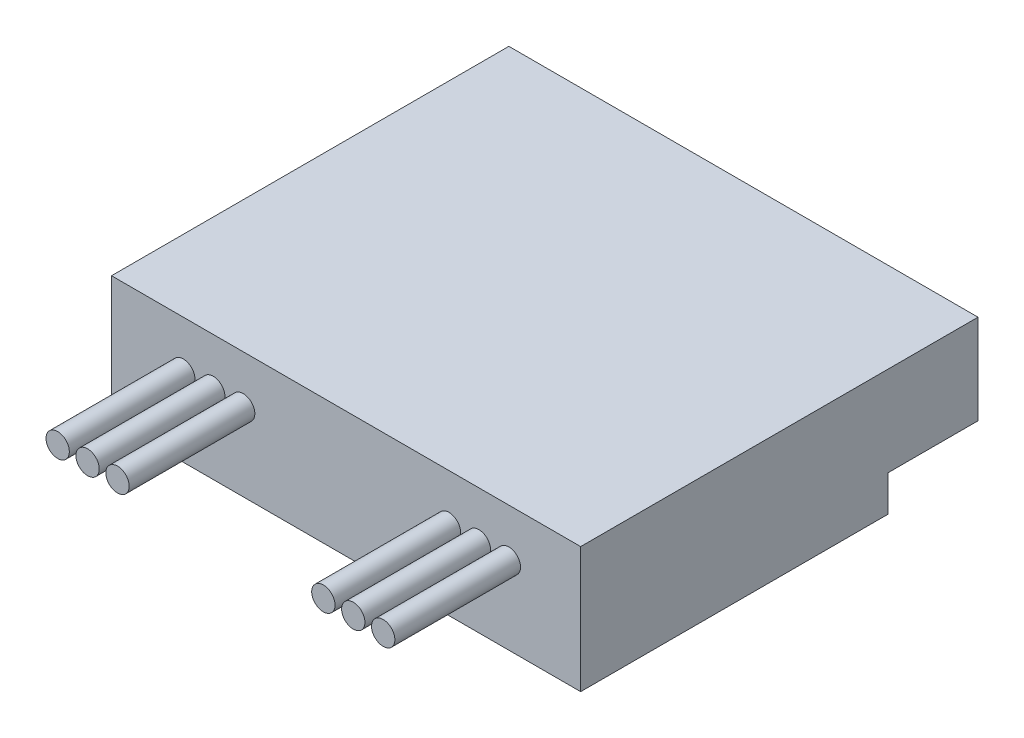
SolidWorks part; units mm, degrees
ref_plane "Front Plane" through (0, 0, 0) normal (0, 0, 1) x (1, 0, 0)
ref_plane "Top Plane" through (0, 0, 0) normal (0, 1, 0) x (1, 0, 0)
ref_plane "Right Plane" through (0, 0, 0) normal (1, 0, 0) x (0, 0, -1)
sketch "Sketch1" plane through (0, 0, 0) normal (0, 1, 0) x (1, 0, 0)
  line L1 (0, 0) -> (78.4, 0)
  line L2 (0, 0) -> (0, 66.4)
  line L3 (0, 66.4) -> (78.4, 66.4)
  line L4 (78.4, 0) -> (78.4, 66.4)
  dimension "D1" = 78.4
  dimension "D2" = 66.4
extrude "Boss-Extrude1" add sketch "Sketch1" along normal blind 21
sketch "Sketch2" plane through (0, 0, 0) normal (0, 0, 1) x (1, 0, 0)
  line L0 (0, 21) -> (0, 0) construction
  line L1 (0, 21) -> (78.4, 21) construction
  line L2 (39.2, 21) -> (39.2, 0) construction
  line L3 (0, 0) -> (78.4, 0) construction
  circle A0 centre (17, 13) radius 1.95
  circle A1 centre (12, 13) radius 1.95
  circle A2 centre (22, 13) radius 1.95
  circle A3 centre (56.4, 13) radius 1.95
  circle A4 centre (61.4, 13) radius 1.95
  circle A5 centre (66.4, 13) radius 1.95
  dimension "D1" = 3.9
  dimension "D2" = 12
  dimension "D3" = 5
  dimension "D4" = 5
  dimension "D5" = 8
extrude "Boss-Extrude2" add sketch "Sketch2" along normal blind 21
sketch "Sketch3" plane through (0, 0, 0) normal (0, -1, 0) x (1, 0, 0)
  line L0 (0, -66.4) -> (0, 0) construction
  line L1 (20, -51.4) -> (52, -51.4)
  line L2 (20, -51.4) -> (20, -31.4)
  line L3 (20, -31.4) -> (52, -31.4)
  line L4 (52, -51.4) -> (52, -31.4)
  line L5 (78.4, -66.4) -> (0, -66.4) construction
  dimension "D1" = 20
  dimension "D2" = 15
  dimension "D3" = 20
  dimension "D4" = 32
extrude "Cut-Extrude1" cut sketch "Sketch3" against normal blind 10
sketch "Sketch4" plane through (0, 0, 0) normal (0, -1, 0) x (1, 0, 0)
  line L0 (78.4, 0) -> (78.4, -66.4) construction
  line L1 (0, -66.4) -> (78.4, -66.4)
  line L2 (0, -66.4) -> (0, -51.4)
  line L3 (0, -51.4) -> (78.4, -51.4)
  line L4 (78.4, -66.4) -> (78.4, -51.4)
  dimension "D1" = 15
extrude "Cut-Extrude2" cut sketch "Sketch4" against normal blind 6
sketch "Sketch5" plane through (0, 10, 0) normal (0, -1, 0) x (1, 0, 0)
  line L2 (52, -31.4) -> (20, -31.4) construction
  line L3 (52, -51.4) -> (52, -31.4) construction
  circle A0 centre (49.05, -34.35) radius 1.95
  circle A1 centre (34.15, -34.35) radius 1.95
  point P6 (0, 0)
  point P7 (0, 0)
  dimension "D1" = 14.9
  dimension "D2" = 3.9
  dimension "D3" = 3.9
  dimension "D4" = 2.95
  dimension "D5" = 2.95
extrude "Boss-Extrude6" add sketch "Sketch5" along normal blind 9
